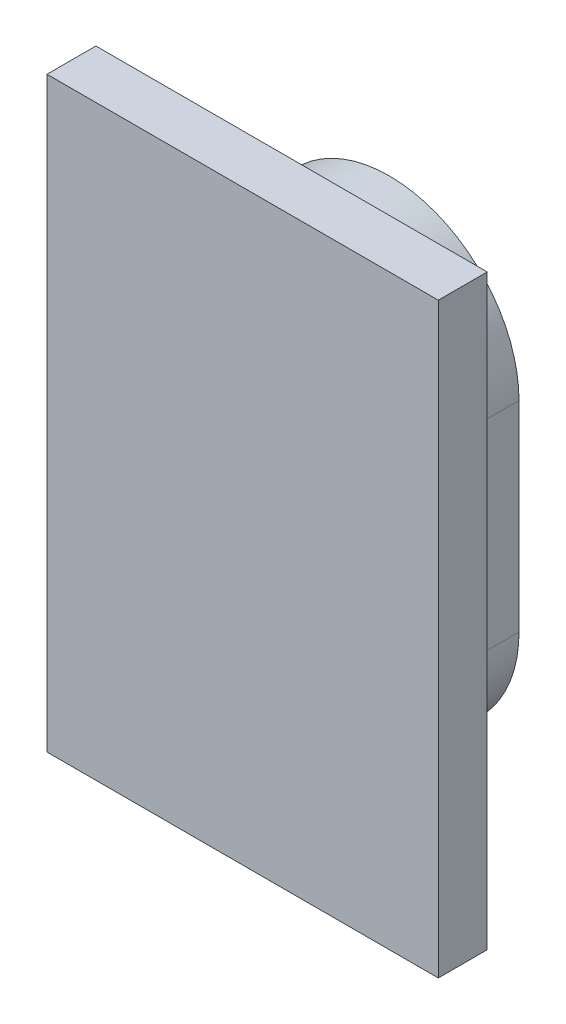
SolidWorks part; units mm, degrees
ref_plane "Front Plane" through (0, 0, 0) normal (0, 0, 1) x (1, 0, 0)
ref_plane "Top Plane" through (0, 0, 0) normal (0, 1, 0) x (1, 0, 0)
ref_plane "Right Plane" through (0, 0, 0) normal (1, 0, 0) x (0, 0, -1)
sketch "Sketch1" plane through (0, 0, 0) normal (0, 0, 1) x (1, 0, 0)
  line L1 (-19.6138, 16.2133) -> (20.3862, 16.2133)
  line L2 (-19.6138, 16.2133) -> (-19.6138, -43.7867)
  line L3 (-19.6138, -43.7867) -> (20.3862, -43.7867)
  line L4 (20.3862, 16.2133) -> (20.3862, -43.7867)
  dimension "D1" = 40
  dimension "D2" = 60
extrude "Boss-Extrude1" add sketch "Sketch1" along normal blind 5
sketch "Sketch4" plane through (0, 0, 0) normal (0, 0, -1) x (-1, 0, 0)
  line L0 (-0.3862, -28.7867) -> (-0.3862, 49971.2133) construction
  line L3 (19.6138, -43.7867) -> (-20.3862, -43.7867) construction
  line L4 (-15.3862, -13.7867) -> (49984.6138, -13.7867) construction
  line L5 (-20.3862, -43.7867) -> (-20.3862, 16.2133) construction
  line L6 (-0.3862, -3.5367) -> (-0.3862, -24.0367) construction
  line L7 (12.8638, -3.5367) -> (12.8638, -24.0367)
  line L8 (-13.6362, -3.5367) -> (-13.6362, -24.0367)
  line L9 (10.3638, -3.5367) -> (10.3638, -24.0367)
  line L10 (-11.1362, -3.5367) -> (-11.1362, -24.0367)
  arc A0 (12.8638, -3.5367) -> (-13.6362, -3.5367) centre (-0.3862, -3.5367) ccw
  arc A1 (-13.6362, -24.0367) -> (12.8638, -24.0367) centre (-0.3862, -24.0367) ccw
  arc A2 (-11.1362, -24.0367) -> (10.3638, -24.0367) centre (-0.3862, -24.0367) ccw
  arc A3 (10.3638, -3.5367) -> (-11.1362, -3.5367) centre (-0.3862, -3.5367) ccw
  point P4 (-0.3862, -43.7867)
  point P9 (-20.3862, -13.7867)
  point P12 (-0.3862, -13.7867)
  dimension "D1" = 2.5
extrude "Boss-Extrude2" add sketch "Sketch4" along normal blind 10
